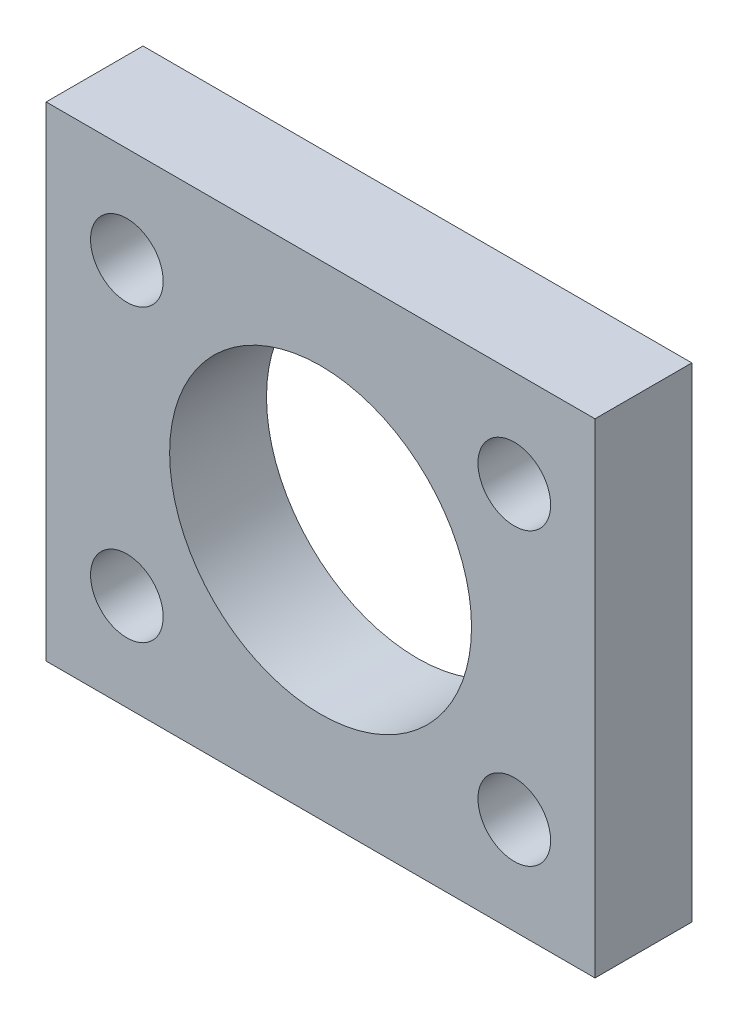
SolidWorks part; units mm, degrees
ref_plane "Front Plane" through (0, 0, 0) normal (0, 0, 1) x (1, 0, 0)
ref_plane "Top Plane" through (0, 0, 0) normal (0, 1, 0) x (1, 0, 0)
ref_plane "Right Plane" through (0, 0, 0) normal (1, 0, 0) x (0, 0, -1)
sketch "Sketch2" plane through (0, 0, 0) normal (0, 0, 1) x (1, 0, 0)
  line L1 (-17, 15) -> (17, 15)
  line L2 (-17, 15) -> (-17, -15)
  line L3 (-17, -15) -> (17, -15)
  line L4 (17, 15) -> (17, -15)
  line L5 (-17, 15) -> (17, -15) construction
  line L6 (-17, -15) -> (17, 15) construction
  point P0 (0, 0)
  dimension "D1" = 34
  dimension "D2" = 30
extrude "Boss-Extrude1" add sketch "Sketch2" along normal blind 6
sketch "Sketch3" plane through (0, 0, 0) normal (0, 0, -1) x (-1, 0, 0)
  line L0 (0, 15) -> (0, -15) construction
  line L1 (-17, 15) -> (17, 15) construction
  line L2 (17, -15) -> (-17, -15) construction
  line L3 (-17, 0) -> (17, 0) construction
  line L4 (-17, -15) -> (-17, 15) construction
  line L5 (17, 15) -> (17, -15) construction
  circle A0 centre (-12, 9) radius 2.25
  circle A1 centre (12, 9) radius 2.25
  circle A2 centre (12, -9) radius 2.25
  circle A3 centre (-12, -9) radius 2.25
  dimension "D1" = 4.5
  dimension "D2" = 6
  dimension "D3" = 5
extrude "Cut-Extrude1" cut sketch "Sketch3" against normal blind 10
sketch "Sketch4" plane through (0, 0, 0) normal (0, 0, -1) x (-1, 0, 0)
  circle A1 centre (0, 0) radius 9.35
  dimension "D2" = 18.7
extrude "Cut-Extrude2" cut sketch "Sketch4" against normal blind 10
